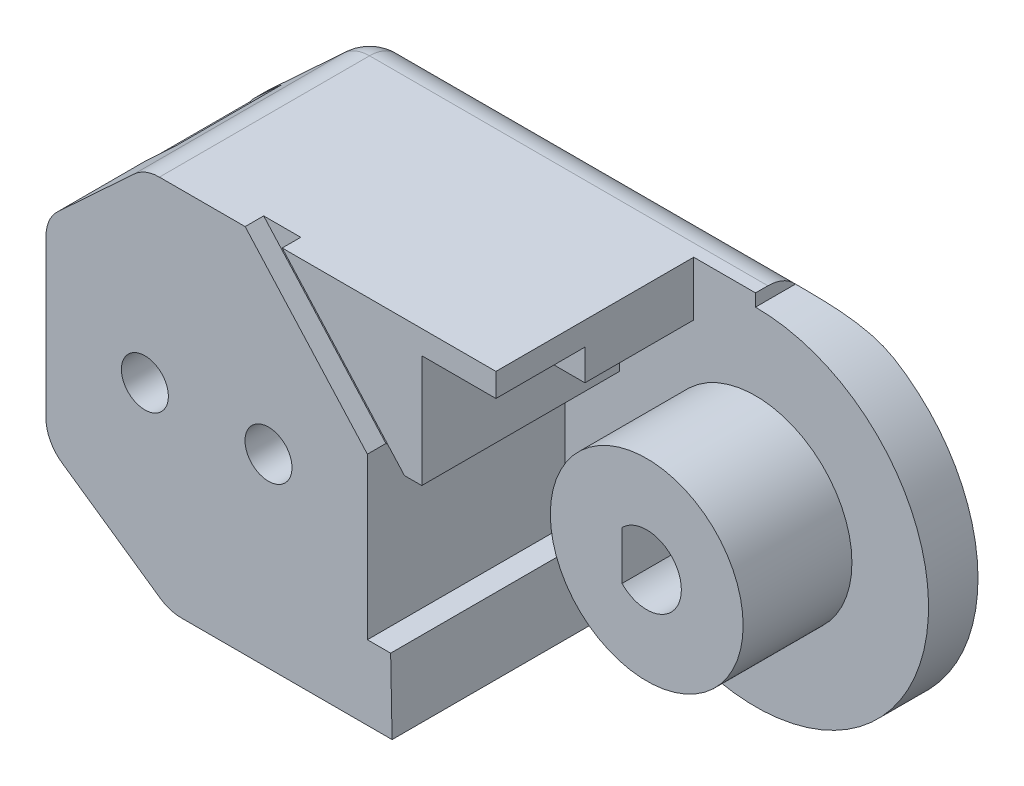
SolidWorks part; units mm, degrees
ref_plane "Front Plane" through (0, 0, 0) normal (0, 0, 1) x (1, 0, 0)
ref_plane "Top Plane" through (0, 0, 0) normal (0, 1, 0) x (1, 0, 0)
ref_plane "Right Plane" through (0, 0, 0) normal (1, 0, 0) x (0, 0, -1)
sketch "Sketch2" plane through (0, 0, 0) normal (0, 0, 1) x (1, 0, 0)
  line L1 (-2.5, 7.5) -> (-16.7, 7.5)
  line L2 (-20.7, 3.7934) -> (-20.7, -4.0316)
  line L3 (-15.7, -7.5) -> (-6.7, -7.5)
  line L4 (-6.7, -7.5) -> (-4.2, -5.6)
  line L5 (-2.5, 7.5) -> (0, 7.5)
  line L7 (0, 7) -> (0, 7.5)
  line L8 (-20.7, 3.7934) -> (-16.7, 7.5)
  line L9 (-20.7, -4.0316) -> (-15.7, -7.5)
  arc A1 (-4.2, -5.6) -> (7, 0) centre (0, 0) ccw
  arc A2 (7, 0) -> (0, 7) centre (0, 0) ccw
  dimension "D1" = 7
  dimension "D2" = 4
  dimension "D3" = 5
  dimension "D4" = 7.5
  dimension "D5" = 15
  dimension "D7" = 2.5
  dimension "D8" = 14
extrude "Boss-Extrude1" add sketch "Sketch2" along normal blind 2 contours A1 A2 L7 L5 L1 L8 L2 L9 L3 L4
sketch "Sketch4" plane through (0, 0, 2) normal (0, 0, 1) x (1, 0, 0)
  line L7 (-15.7, -7.5) -> (-6.7, -7.5)
  line L8 (-6.7, -7.5) -> (-6.7591, -4.5)
  line L9 (-6.7591, -4.5) -> (-7.7, -4.5)
  line L10 (-16.7, 7.5) -> (-2.5, 7.5)
  line L13 (-5.5, 2) -> (-5.5, 5.3)
  line L14 (-5.5, 5.3) -> (-2.5, 5.3)
  line L21 (-20.7, -4.0316) -> (-15.7, -7.5)
  line L24 (-16.7, 7.5) -> (-20.7, 3.7934)
  line L25 (-20.7, -4.0316) -> (-20.7, 3.7934)
  line L26 (-7.7, 2) -> (-5.5, 2)
  line L29 (-7.7, 2) -> (-7.7, -4.5)
  line L30 (-2.5, 7.5) -> (-2.5, 5.3)
  point P2 (-5.5, 3.65)
  dimension "D1" = 13
  dimension "D2" = 2.5
  dimension "D3" = 3
  dimension "D4" = 3
  dimension "D5" = 3.3
  dimension "D6" = 2.2
extrude "Boss-Extrude2" add sketch "Sketch4" along normal blind 8
ref_point "Point1"
sketch "Sketch22" plane through (0, 0, 2) normal (0, 0, 1) x (1, 0, 0)
  line L0 (0, 5.3) -> (-14, 5.3) construction
  line L1 (0, 4) -> (-14, 4) construction
  line L2 (-14, 4) -> (-14, 5.3) construction
  circle A0 centre (0, 0) radius 5.3 construction
  circle A1 centre (0, 0) radius 4 construction
  dimension "D1" = 14
  dimension "D2" = 10.6
  dimension "D3" = 8
sketch "Sketch24" plane through (0, 0, 2) normal (0, 0, 1) x (1, 0, 0)
  circle A0 centre (0, 0) radius 3.9
  dimension "D1" = 7.8
extrude "Boss-Extrude5" add sketch "Sketch24" along normal blind 4.4
sketch "Sketch29" plane through (-5.5, 0, 0) normal (1, 0, 0) x (0, 0, -1)
  line L0 (-1.9279, 3.9758) -> (-10, 3.9758) construction
  line L1 (-10, 2) -> (-10, 5.3) construction
sketch "Sketch30" plane through (-5.5, 0, 0) normal (1, 0, 0) x (0, 0, -1)
  line L0 (-6.4086, 3.9758) -> (-6.4086, 5.3)
  line L1 (-6.4086, 3.9758) -> (-2, 3.9758)
  line L2 (-6.4086, 5.3) -> (-2, 5.3)
  line L3 (-2, 3.9758) -> (-2, 5.3)
  line L6 (-2, 2) -> (-2, 5.3) construction
  line L7 (-10, 5.3) -> (-2, 5.3) construction
  dimension "D1" = 4.4086
extrude "Cut-Extrude12" cut sketch "Sketch30" against normal blind 16
ref_plane "Plane1" through (0, 0, 10) normal (0, 0, 1) x (1, 0, 0)
sketch "Sketch8" plane through (0, 0, 2) normal (0, 0, 1) x (1, 0, 0)
  circle A1 centre (0, 0) radius 3.8
  circle A2 centre (0, 0) radius 2.5
sketch "Sketch28" plane through (0, 0, 6.4) normal (0, 0, 1) x (1, 0, 0)
  line L0 (-1, 0.9798) -> (-1, -0.9798)
  arc A0 (-1, -0.9798) -> (-1, 0.9798) centre (0, 0) ccw
  dimension "D1" = 1
  dimension "D2" = 1.4
extrude "Cut-Extrude11" cut sketch "Sketch28" against normal through all
sketch "Sketch33" plane through (0, 0, 10) normal (0, 0, 1) x (1, 0, 0)
  line L0 (-7, 2) -> (-0.5657, -5.1566) construction
  line L2 (-8.2591, -4.5) -> (-2.6001, 3.0469) construction
  dimension "D1" = 1.5
  dimension "D2" = 1.5
fillet "Fillet1" radius 1.5 9 edges at (-11.2, -7.5, 0) (-8.35, 7.5, 0) (-18.7, 5.6467, 0) (-18.2, -5.7658, 0) (-20.7, -0.1191, 0) (-15.7, -7.5, 5) (-20.7, -4.0316, 5) (-20.7, 3.7934, 5) (-16.7, 7.5, 5)
sketch "Sketch34" plane through (0, 2, 0) normal (0, -1, 0) x (1, 0, 0)
  line L4 (-7.7, 10) -> (-5.5, 10) construction
  line L5 (-6.2, 10.75) -> (-7.7, 10.75)
  line L6 (-6.2, 10.75) -> (-6.2, 9.25)
  line L7 (-6.2, 9.25) -> (-7.7, 9.25)
  line L8 (-7.7, 10.75) -> (-7.7, 9.25)
  line L9 (-6.2, 10.75) -> (-7.7, 9.25) construction
  line L10 (-6.2, 9.25) -> (-7.7, 10.75) construction
  line L12 (-7.7, 10) -> (-7.7, 2) construction
  point P0 (-6.95, 10)
  dimension "D1" = 1.5
  dimension "D2" = 1.5
extrude "Cut-Extrude13" cut sketch "Sketch34" along direction (0.6686, -0.7436, 0) on the side against the normal blind 8
sketch "Sketch35" plane through (0, -4.5, 0) normal (0, 1, 0) x (1, 0, 0)
  circle A0 centre (-8.2591, -10) radius 0.75
sketch "Sketch36" plane through (0, 0, 10) normal (0, 0, 1) x (1, 0, 0)
  line L0 (-20.7, 3.1384) -> (-20.7, -3.2466) construction
  line L1 (-12.6449, 7.5) -> (-16.1119, 7.5) construction
  line L2 (-7.7, -4.5) -> (-7.7, 2) construction
  circle A0 centre (-11.7, 0) radius 0.95
  circle A1 centre (-16.7, 0) radius 0.95
  dimension "D1" = 4
  dimension "D2" = 5
  dimension "D5" = 1.9
  dimension "D3" = 4
  dimension "D4" = 7.5
extrude "Cut-Extrude15" cut sketch "Sketch36" against normal blind 8
sketch "Sketch37" plane through (0, 0, 0) normal (0, 0, -1) x (-1, 0, 0)
  circle A0 centre (11.7, 0) radius 2
  circle A1 centre (16.7, 0) radius 2
  dimension "D1" = 4
extrude "Cut-Extrude16" cut sketch "Sketch37" against normal blind 4.5
sketch "Sketch38" plane through (0, 0, 10) normal (0, 0, 1) x (1, 0, 0)
  line L0 (-5.5, 5.3) -> (-2.5, 5.3)
  line L1 (-5.5, 5.3) -> (-5.5, 6.55)
  line L2 (-2.5, 5.3) -> (-2.5, 6.55)
  line L3 (-5.5, 6.55) -> (-2.5, 6.55)
  dimension "D1" = 1.25
extrude "Cut-Extrude17" cut sketch "Sketch38" against normal blind 3.6
ref_plane "Plane2" through (0, 0, 6.4) normal (0, 0, 1) x (1, 0, 0)
